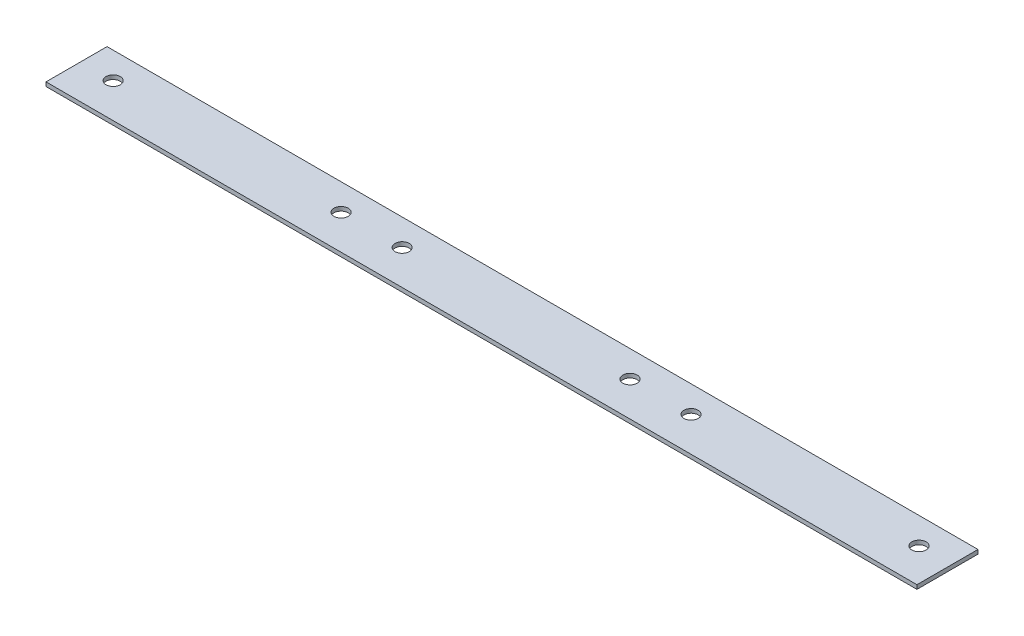
SolidWorks part; units mm, degrees
material "Простая углеродистая сталь"
ref_plane "Спереди" through (0, 0, 0) normal (0, 0, 1) x (1, 0, 0)
ref_plane "Сверху" through (0, 0, 0) normal (0, 1, 0) x (1, 0, 0)
ref_plane "Справа" through (0, 0, 0) normal (1, 0, 0) x (0, 0, -1)
sketch "Эскиз1" plane through (0, 0, 0) normal (0, 1, 0) x (1, 0, 0)
  line L1 (0, 0) -> (214, 0)
  line L2 (0, 0) -> (0, 15)
  line L3 (0, 15) -> (214, 15)
  line L4 (214, 0) -> (214, 15)
  circle A2 centre (64, 8.5) radius 1.75
  circle A3 centre (8, 8.5) radius 1.75
  circle A4 centre (79, 8.5) radius 1.75
  circle A5 centre (135, 8.5) radius 1.75
  circle A6 centre (150, 8.5) radius 1.75
  circle A7 centre (206, 8.5) radius 1.75
  point P7 (7.9704, 8.0829)
  dimension "D1" = 3
extrude "Бобышка-Вытянуть1" add sketch "Эскиз1" along normal blind 1
